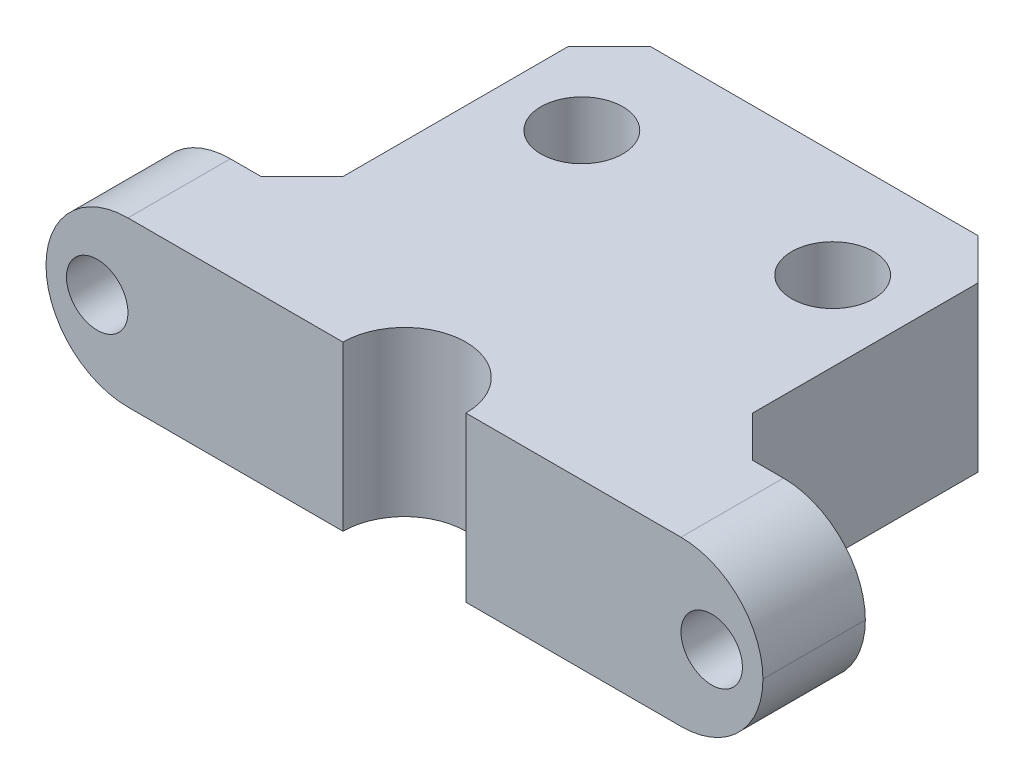
SolidWorks part; units mm, degrees
ref_plane "Front" through (0, 0, 0) normal (0, 0, 1) x (1, 0, 0)
ref_plane "Top" through (0, 0, 0) normal (0, 1, 0) x (1, 0, 0)
ref_plane "Right" through (0, 0, 0) normal (1, 0, 0) x (0, 0, -1)
sketch "Sketch1" plane through (0, 0, 0) normal (0, 1, 0) x (1, 0, 0)
  line L0 (0, 0) -> (0, 12.4219) construction
  line L1 (-17.5, 20) -> (17.5, 20)
  line L2 (-17.5, 20) -> (-17.5, 0)
  line L3 (-17.5, 0) -> (17.5, 0)
  line L4 (17.5, 20) -> (17.5, 0)
  line L5 (-17.5, 20) -> (17.5, 0) construction
  line L6 (-17.5, 0) -> (17.5, 20) construction
  line L7 (-17.5, 20) -> (-10, 20)
  line L8 (-17.5, 20) -> (-17.5, 5)
  line L9 (-17.5, 5) -> (-10, 5)
  line L10 (-10, 20) -> (-10, 5)
  line L11 (17.5, 20) -> (10, 20)
  line L12 (17.5, 20) -> (17.5, 5)
  line L13 (17.5, 5) -> (10, 5)
  line L14 (10, 20) -> (10, 5)
  circle A0 centre (0, 0) radius 3
  point P3 (0, 10)
  dimension "D1" = 6
  dimension "D2" = 20
  dimension "D3" = 35
  dimension "D4" = 20
  dimension "D5" = 5
extrude "Boss-Extrude1" add sketch "Sketch1" along normal blind 8 contours A0 L3 L4 L13 L14 L1 L10 L9 L2 region at (0, 0, -9.0472)
chamfer "Chamfer1" distance 2 angle 45 2 edges at (10, 4, -5) (-10, 4, -5)
sketch "Sketch2" plane through (0, 0, -5) normal (0, 0, -1) x (-1, 0, 0)
  line L0 (0, 0) -> (0, 4) construction
  line L1 (10, 0) -> (-10, 0) construction
  line L2 (-15, 4) -> (15, 4) construction
  line L5 (-17.5, 8) -> (-12, 8) construction
  circle A0 centre (-15, 4) radius 1.5
  circle A1 centre (15, 4) radius 1.5
  dimension "D2" = 3
  dimension "D1" = 4
  dimension "D3" = 30
extrude "Cut-Extrude1" cut sketch "Sketch2" against normal through all
fillet "Fillet1" radius 4 4 edges at (17.5, 8, -2.5) (-17.5, 8, -2.5) (17.5, 0, -2.5) (-17.5, 0, -2.5)
sketch "Sketch3" plane through (0, 8, 0) normal (0, 1, 0) x (1, 0, 0)
  line L0 (-6.1229, 14.7821) -> (6.1229, 14.7821) construction
  line L1 (0, 0) -> (0, 14.7821) construction
  circle A0 centre (-6.1229, 14.7821) radius 2
  circle A1 centre (6.1229, 14.7821) radius 2
  dimension "D1" = 4
  dimension "D2" = 45
  dimension "D3" = 16
extrude "Cut-Extrude2" cut sketch "Sketch3" against normal through all
chamfer "Chamfer2" distance 2 angle 45 2 edges at (-10, 4, -20) (10, 4, -20)
